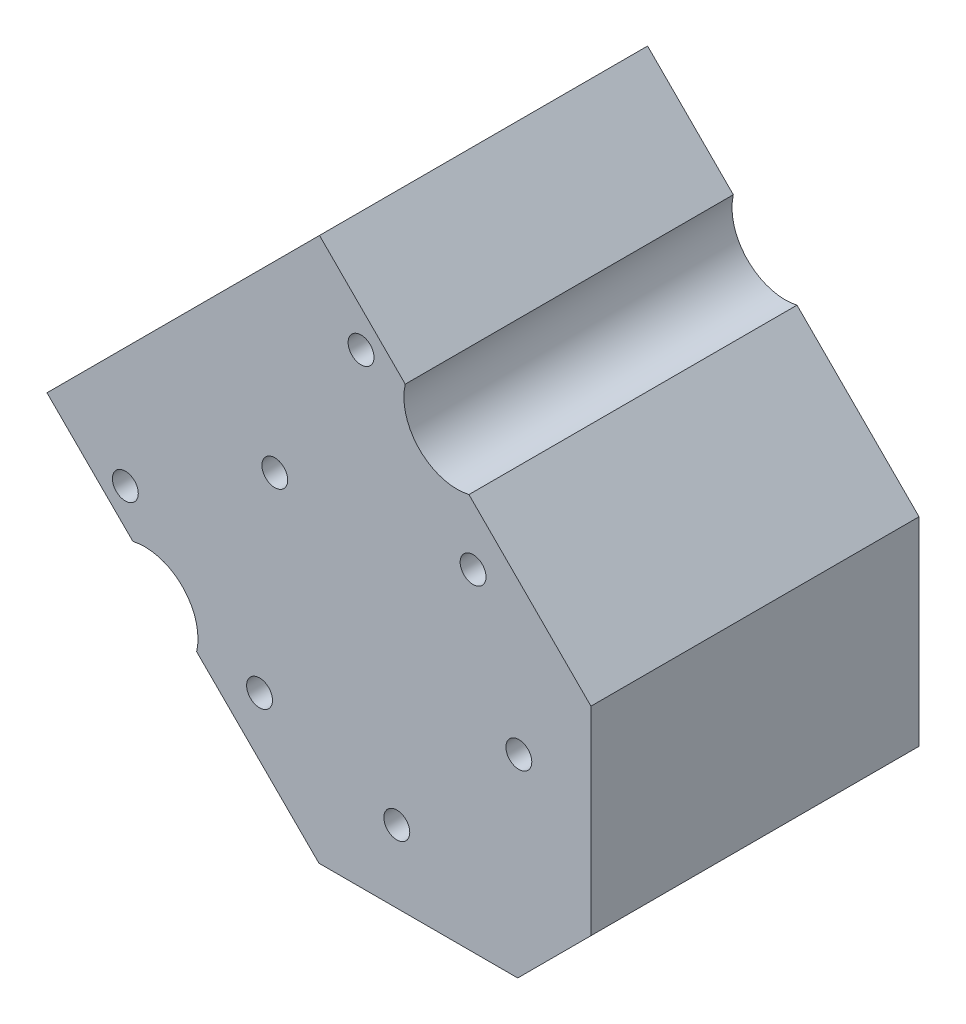
SolidWorks part; units mm, degrees
ref_plane "Front Plane" through (0, 0, 0) normal (0, 0, 1) x (1, 0, 0)
ref_plane "Top Plane" through (0, 0, 0) normal (0, 1, 0) x (1, 0, 0)
ref_plane "Right Plane" through (0, 0, 0) normal (1, 0, 0) x (0, 0, -1)
sketch "Sketch1" plane through (0, 0, 0) normal (0, 0, 1) x (1, 0, 0)
  line L0 (0, 0) -> (0, 73.5) construction
  line L1 (-96.5, -48) -> (-73.5, -48) construction
  line L2 (-96.5, -48) -> (-96.5, 52) construction
  line L4 (-73.5, -48) -> (-73.5, 27) construction
  line L5 (-52, 96.5) -> (48, 96.5) construction
  line L7 (-27, 73.5) -> (48, 73.5) construction
  line L8 (48, 96.5) -> (48, 73.5) construction
  line L9 (0, 0) -> (-73.5, 0) construction
  line L10 (-27, 73.5) -> (-73.5, 27) construction
  line L11 (-73.5, 73.5) -> (-27, 73.5) construction
  line L12 (-73.5, 27) -> (-73.5, 73.5) construction
  line L13 (-58.4584, 90.0416) -> (-90.0416, 58.4584)
  line L14 (-96.5, 96.5) -> (-52, 96.5) construction
  line L15 (-96.5, 52) -> (-96.5, 96.5) construction
  line L16 (-24.3179, 73.5) -> (-25, 73.5) construction
  line L17 (23.2069, 73.5) -> (48, 73.5) construction
  line L18 (-73.5, 25) -> (-73.5, 24.3179) construction
  line L19 (-73.5, -48) -> (-73.5, -23.2069) construction
  line L20 (-73.5, 23.2069) -> (-73.5, -23.2069) construction
  line L21 (-23.2069, 73.5) -> (23.2069, 73.5) construction
  line L22 (-58.5251, 27) -> (-35.4853, 27)
  line L23 (-27, 35.4853) -> (-27, 58.5251)
  line L24 (-35.4853, 27) -> (-27, 35.4853)
  line L25 (-25, 73.5) -> (-27, 73.5) construction
  line L26 (-27, 71.5) -> (-27, 73.5) construction
  line L27 (-73.5, 27) -> (-73.5, 25) construction
  line L28 (-73.5, 27) -> (-71.5, 27) construction
  line L29 (-23.2069, 73.5) -> (-24.3179, 73.5) construction
  line L30 (-73.5, 24.3179) -> (-73.5, 23.2069) construction
  line L31 (-27, 71.5) -> (-27, 73.5) construction
  line L32 (-27, 96.5) -> (-52, 96.5) construction
  line L33 (-71.5, 27) -> (-73.5, 27) construction
  line L34 (-96.5, 52) -> (-96.5, 27) construction
  line L35 (-27, 58.5251) -> (-41.1411, 72.6923)
  line L36 (-52, 96.5) -> (-58.4584, 90.0416) construction
  line L37 (-27, 73.5) -> (-27, 96.5) construction
  line L38 (-27, 58.5251) -> (-27, 71.5) construction
  line L39 (0, 0) -> (-80.9943, 80.9943) construction
  line L40 (-58.5251, 27) -> (-72.6923, 41.1411)
  line L41 (-71.5, 27) -> (-58.5251, 27) construction
  line L42 (-90.0416, 58.4584) -> (-96.5, 52) construction
  line L43 (-73.5, 27) -> (-96.5, 27) construction
  line L44 (-48.5208, 80.0857) -> (-58.4584, 90.0416)
  line L47 (-80.0857, 48.5208) -> (-90.0416, 58.4584)
  line L48 (-66.0195, 34.4805) -> (-80.0857, 48.5208) construction
  line L49 (-72.6923, 41.1411) -> (-66.0195, 34.4805) construction
  arc A0 (23.2069, 73.5) -> (-22.3981, 74.1947) centre (0, 47.3) ccw construction
  arc A1 (-74.1947, 22.3981) -> (-73.5, -23.2069) centre (-47.3, 0) ccw construction
  arc A2 (-25, 73.5) -> (-27, 71.5) centre (-25, 71.5) ccw construction
  arc A3 (-71.5, 27) -> (-73.5, 25) centre (-71.5, 25) ccw construction
  arc A4 (-24.3179, 73.5) -> (-22.3981, 74.1947) centre (-24.3179, 76.5) ccw construction
  arc A5 (-22.3981, 74.1947) -> (-23.2069, 73.5) centre (0, 47.3) ccw construction
  arc A6 (-73.5, 24.3179) -> (-74.1947, 22.3981) centre (-76.5, 24.3179) cw construction
  arc A7 (-73.5, 23.2069) -> (-74.1947, 22.3981) centre (-47.3, 0) ccw construction
  arc A8 (-48.5208, 80.0857) -> (-41.1411, 72.6923) centre (-42.503, 78.7127) ccw
  arc A9 (-80.0857, 48.5208) -> (-72.6923, 41.1411) centre (-78.7127, 42.503) cw
  dimension "D6" = 35
  dimension "D10" = 2
  dimension "D11" = 3
  dimension "D1" = 135
  dimension "D2" = 23
  dimension "D3" = 73.5
  dimension "D4" = 48
  dimension "D8" = 27
  dimension "D9" = 12
  dimension "D5" = 100
  dimension "D7" = 26.2
extrude "Boss-Extrude1" add sketch "Sketch1" along normal blind 38.0226
ref_axis "Axis1" through (0, 0, -1.9011) along (0, 0, 1)
sketch "Sketch4" plane through (0, 0, 38.0226) normal (0, 0, 1) x (1, 0, 0)
  line L0 (0, 0) -> (0, 52.0101) construction
  line L1 (0, 0) -> (-63.6396, 63.6396) construction
  line L2 (0, 0) -> (-52.0101, 0) construction
  line L5 (-80.9601, 53.6396) -> (-63.6396, 63.6396) construction
  line L6 (-63.6396, 63.6396) -> (-83.2677, 83.2677) construction
  line L8 (-65.4074, 40.6586) -> (-40.6586, 65.4074) construction
  line L9 (-35.3553, 49.4975) -> (-49.4975, 35.3553) construction
  line L11 (-35.4853, 27) -> (-27, 35.4853) construction
  circle A1 centre (-63.6396, 63.6396) radius 1.5
  circle A3 centre (-80.9601, 53.6396) radius 1.5
  circle A4 centre (-53.6396, 80.9601) radius 1.5
  circle A9 centre (-40.6586, 65.4074) radius 1.5
  circle A10 centre (-65.4074, 40.6586) radius 1.5
  circle A11 centre (-49.4975, 35.3553) radius 1.5
  circle A12 centre (-35.3553, 49.4975) radius 1.5
  dimension "D2" = 20
  dimension "D3" = 3
  dimension "D1" = 45
  dimension "D6" = 45.8162
  dimension "D7" = 75
  dimension "D9" = 35
  dimension "D10" = 20
  dimension "D11" = 15
  dimension "D12" = 15
extrude "Cut-Extrude2" cut sketch "Sketch4" against normal through all
equation "\"EyeDiameter\" = 35"
equation "\"BasePlaneDistance\" = \"EyeDiameter\"/2+19.84"
equation "\"EyeClearance\" = 2"
equation "\"L2Thickness\" = 8"
equation "\"L2_ID\" = 20"
equation "\"Offset\"= - 2"
equation "\"D3@Sketch1\"=\"BasePlaneDistance\" + 38.16 +\"Offset\""
equation "\"D7@Sketch1\"=24.20 - \"Offset\""
equation "\"D2@Sketch1\"=25.00 + \"Offset\""
